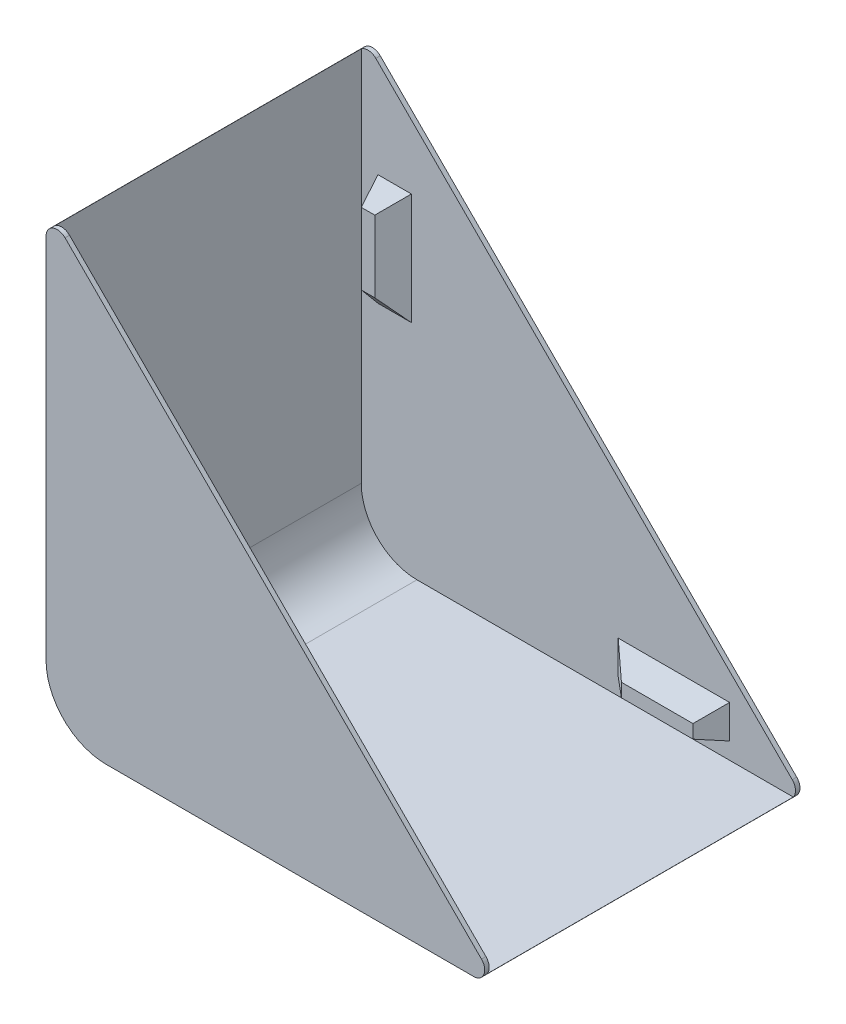
SolidWorks part; units mm, degrees
ref_plane "Plan de face" through (0, 0, 0) normal (0, 0, 1) x (1, 0, 0)
ref_plane "Plan de dessus" through (0, 0, 0) normal (0, 1, 0) x (1, 0, 0)
ref_plane "Plan de droite" through (0, 0, 0) normal (1, 0, 0) x (0, 0, -1)
sketch "Esquisse1" plane through (0, 0, 0) normal (0, 0, 1) x (1, 0, 0)
  line L0 (0, 0) -> (0, 80)
  line L1 (0, 80) -> (80, 0)
  line L2 (80, 0) -> (0, 0)
  dimension "D1" = 80
  dimension "D2" = 80
extrude "Boss.-Extru.1" add sketch "Esquisse1" along normal mid plane 55
sketch "Esquisse4" plane through (0, 0, 0) normal (1, 0, 0) x (0, 0, -1)
  line L0 (-61.9556, 0) -> (61.9556, 0) construction
  point P4 (0, 0)
fillet "Congé1" radius 10 1 edges at (0, 0, 0)
shell "Coque1" thickness 0.8 removed face at (40, 40, 0) outward yes
fillet "Congé2" radius 2 2 edges at (80.8, -0.8, 0) (-0.8, 80.8, 0)
sketch "Esquisse2" plane through (0, 0, 27.5) normal (0, 0, -1) x (-1, 0, 0)
  line L0 (-66.1349, 3) -> (-66.1349, 9)
  line L1 (-66.1349, 3) -> (-46.1349, 3)
  line L2 (-66.1349, 9) -> (-46.1349, 9)
  line L3 (-46.1349, 3) -> (-46.1349, 9)
  line L4 (-10, 0) -> (-77.5716, 0) construction
  line L5 (-3, 39.4964) -> (-3, 59.4964)
  line L6 (-3, 39.4964) -> (-9, 39.4964)
  line L7 (-3, 59.4964) -> (-9, 59.4964)
  line L8 (-9, 39.4964) -> (-9, 59.4964)
  line L9 (0, 77.5716) -> (0, 10) construction
  arc A0 (-77.3858, 2.6142) -> (-77.5716, 0) centre (-75.9716, 1.2) ccw construction
  dimension "D1" = 3
  dimension "D2" = 20
  dimension "D3" = 6
  dimension "D4" = 10
  dimension "D5" = 20
  dimension "D6" = 3
  dimension "D7" = 6
extrude "Boss.-Extru.2" add sketch "Esquisse2" along normal blind 3
chamfer "Chanfrein1" distance 3 angle 50 6 edges at (56.1349, 9, 24.5) (66.1349, 6, 24.5) (46.1349, 6, 24.5) (6, 39.4964, 24.5) (6, 59.4964, 24.5) (9, 49.4964, 24.5) first distance on face at (56.1349, 9, 26) first distance on face at (66.1349, 6, 26) first distance on face at (46.1349, 6, 26) first distance on face at (6, 39.4964, 26) first distance on face at (6, 59.4964, 26) first distance on face at (9, 49.4964, 26)
mirror "Symétrie1" about plane through (0, 0, 0) normal (0, 0, 1) of "Chanfrein1", "Boss.-Extru.2"
equation "\"longueur\"=80"
equation "\"D1@Esquisse1\"=\"longueur\""
equation "\"D2@Esquisse1\"=\"longueur\""
equation "\"largeur_ext\"=10"
equation "\"D1@Boss.-Extru.1\"=\"largeur_int\""
equation "\"largeur_int\"= 55"
equation "\"conges\"=10"
equation "\"D1@Congé1\"=\"conges\""
equation "\"buse\"= 0.4'Buse impression"
equation "\"D1@Coque1\"=\"buse\"*2"
